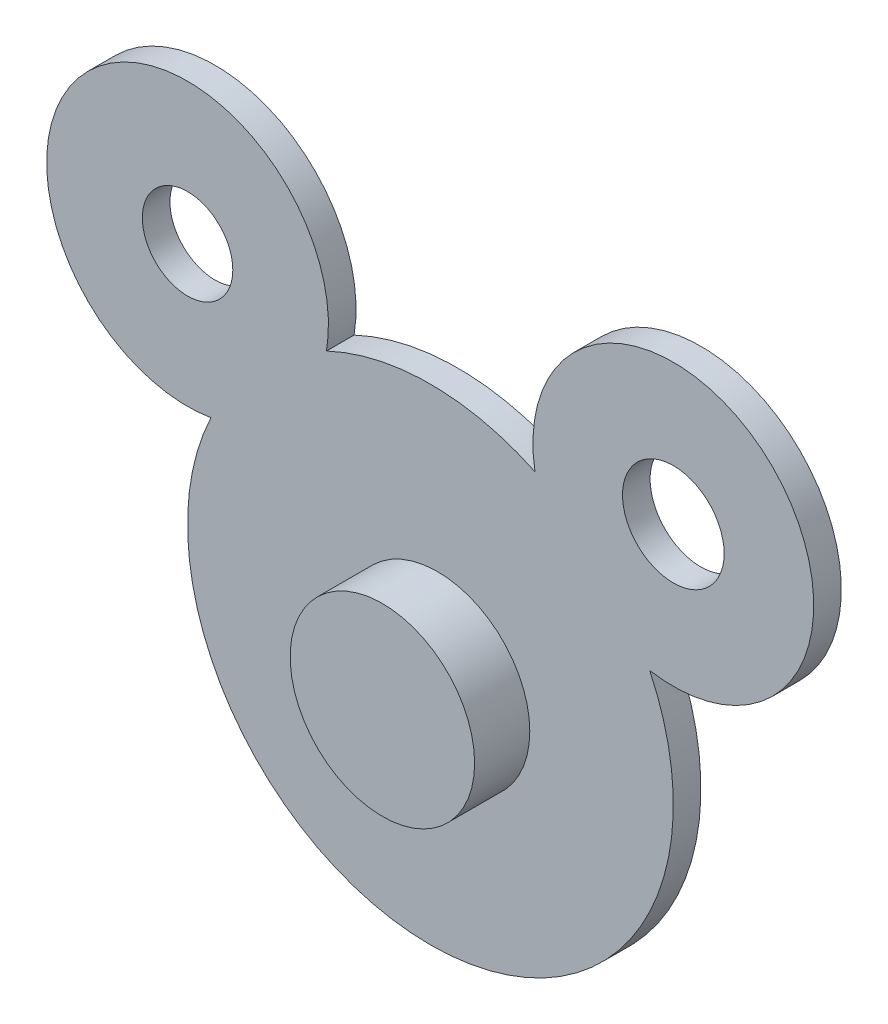
SolidWorks part; units mm, degrees
material "A286 Iron Base Superalloy"
ref_plane "Front Plane" through (0, 0, 0) normal (0, 0, 1) x (1, 0, 0)
ref_plane "Top Plane" through (0, 0, 0) normal (0, 1, 0) x (1, 0, 0)
ref_plane "Right Plane" through (0, 0, 0) normal (1, 0, 0) x (0, 0, -1)
sketch "Sketch1" plane through (0, 0, 0) normal (0, 0, 1) x (1, 0, 0)
  arc A0 (-40.4275, 19.1426) -> (40.3803, 19.242) centre (0, 0) ccw
  arc A1 (-19.1426, 40.4275) -> (-40.4275, 19.1426) centre (-44.7306, 44.7306) ccw
  arc A2 (40.3803, 19.242) -> (19.242, 40.3803) centre (44.7306, 44.7306) ccw
  arc A3 (19.242, 40.3803) -> (-19.1426, 40.4275) centre (0, 0) ccw
  circle A4 centre (-44.7306, 44.7306) radius 8.333
  circle A5 centre (44.7306, 44.7306) radius 9.3584
  dimension "D1" = 89.4611
  dimension "D2" = 51.8945
  dimension "D3" = 51.7143
extrude "Boss-Extrude2" add sketch "Sketch1" along normal blind 5.08
sketch "Sketch2" plane through (0, 0, 5.08) normal (0, 0, 1) x (1, 0, 0)
  circle A0 centre (1.3059, -1.5143) radius 16.9874
  circle A1 centre (1.3059, -1.5143) radius 7.5122
extrude "Boss-Extrude3" add sketch "Sketch2" along normal blind 10.16 contours A0
extrude "Cut-Extrude1" cut sketch "Sketch2<3>" against normal blind 10.16 contours A1
sketch "Sketch2<3>" plane through (0, 0, 5.08) normal (0, 0, 1) x (1, 0, 0) same geometry as "Sketch2"
extrude "Boss-Extrude4" add sketch "Sketch2<4>" along normal through all
sketch "Sketch2<4>" plane through (0, 0, 5.08) normal (0, 0, 1) x (1, 0, 0) same geometry as "Sketch2"
